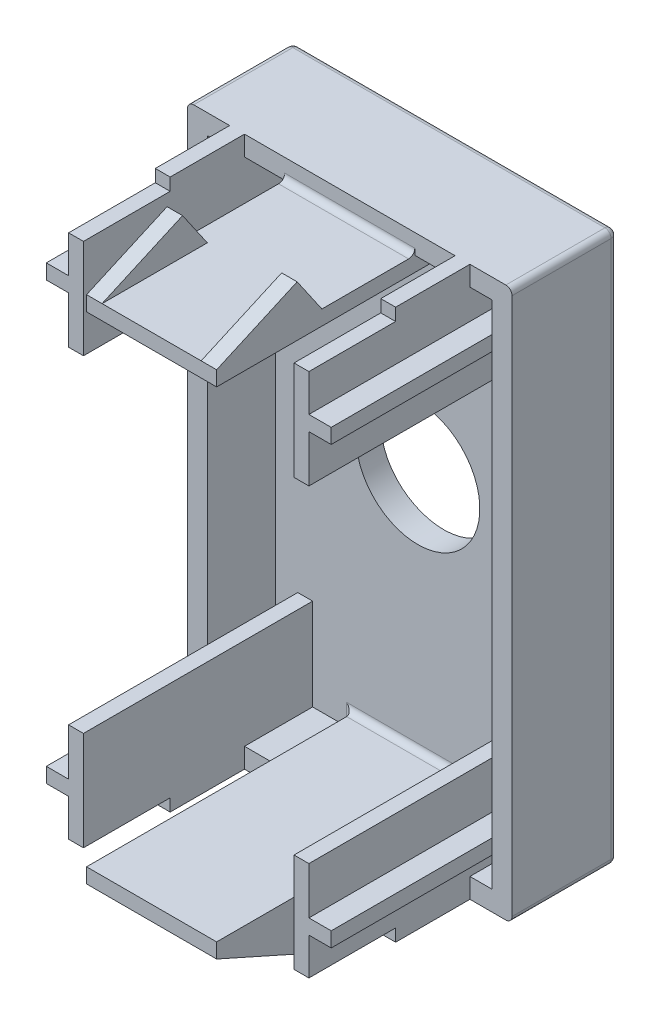
SolidWorks part; units mm, degrees
material "Сталь 3 ГОСТ 535-88"
ref_plane "Спереди" through (0, 0, 0) normal (0, 0, 1) x (1, 0, 0)
ref_plane "Сверху" through (0, 0, 0) normal (0, 1, 0) x (1, 0, 0)
ref_plane "Справа" through (0, 0, 0) normal (1, 0, 0) x (0, 0, -1)
sketch "Эскиз1" plane through (0, 0, 0) normal (0, 0, 1) x (1, 0, 0)
  line L0 (0, 22.2) -> (26.2, 22.2) construction
  line L1 (0, 0) -> (26.2, 0)
  line L2 (0, 0) -> (0, 44.4)
  line L3 (0, 44.4) -> (26.2, 44.4)
  line L4 (26.2, 0) -> (26.2, 44.4)
  circle A0 centre (13.1, 22.2) radius 5
  dimension "D3" = 10
  dimension "D1" = 26.2
  dimension "D2" = 44.4
extrude "Бобышка-Вытянуть1" add sketch "Эскиз1" along normal blind 8.5
ref_plane "Плоскость1" through (3, 0, 0) normal (1, 0, 0) x (0, 0, -1)
sketch "Эскиз2" plane through (3, 0, 0) normal (1, 0, 0) x (0, 0, -1)
  line L0 (0, 0) -> (0, 5) construction
  line L1 (0, 0) -> (0, 44.4) construction
  line L2 (0, 44.4) -> (0, 39.4) construction
  line L3 (0, 39.4) -> (0, 5)
  arc A0 (0, 5) -> (0, 39.4) centre (147.42, 22.2) cw
  dimension "D1" = 5
  dimension "D3" = 1
  dimension "D2" = 5
extrude "Вырез-Вытянуть1" cut sketch "Эскиз2" along normal offset from surface (20.2 mm away) 3 up to face at (26.2, 22.2, 4.25)
sketch "Эскиз3" plane through (0, 0, 8.5) normal (0, 0, 1) x (1, 0, 0)
  line L0 (24.6, 1.6) -> (24.6, 42.8)
  line L1 (26.2, 0) -> (0, 0) construction
  line L2 (26.2, 0) -> (26.2, 44.4) construction
  line L3 (26.2, 44.4) -> (0, 44.4) construction
  line L4 (0, 0) -> (0, 44.4) construction
  line L5 (24.6, 42.8) -> (1.6, 42.8)
  line L6 (1.6, 1.6) -> (1.6, 42.8)
  line L7 (24.6, 1.6) -> (1.6, 1.6)
  dimension "D1" = 1.6
extrude "Вырез-Вытянуть2" cut sketch "Эскиз3" against normal blind 5.5
sketch "Эскиз4" plane through (0, 0, 3) normal (0, 0, 1) x (1, 0, 0)
  line L0 (3.4, 44.4) -> (3.4, 40.4)
  line L1 (24.6, 42.8) -> (1.6, 42.8) construction
  line L2 (3.4, 40.4) -> (1.6, 40.4)
  line L3 (1.6, 42.8) -> (1.6, 1.6) construction
  line L4 (1.6, 40.4) -> (1.6, 39.2)
  line L5 (1.6, 39.2) -> (3.4, 39.2)
  line L6 (3.4, 39.2) -> (3.4, 35.4)
  line L7 (3.4, 35.4) -> (4.6, 35.4)
  line L8 (4.6, 35.4) -> (4.6, 44.4)
  line L10 (4.6, 44.4) -> (3.4, 44.4)
  line L11 (3.4, 39.2) -> (3.4, 40.4) construction
  line L12 (13.1, 42.8) -> (13.1, 1.6) construction
  line L13 (1.6, 1.6) -> (24.6, 1.6) construction
  line L14 (24.6, 22.2) -> (1.6, 22.2) construction
  line L15 (24.6, 1.6) -> (24.6, 42.8) construction
  line L16 (1.6, 42.8) -> (1.6, 1.6) construction
  line L17 (22.8, 39.2) -> (22.8, 40.4) construction
  line L18 (21.6, 44.4) -> (22.8, 44.4)
  line L19 (21.6, 35.4) -> (21.6, 44.4)
  line L20 (22.8, 35.4) -> (21.6, 35.4)
  line L21 (22.8, 39.2) -> (22.8, 35.4)
  line L22 (24.6, 39.2) -> (22.8, 39.2)
  line L23 (24.6, 40.4) -> (24.6, 39.2)
  line L24 (22.8, 40.4) -> (24.6, 40.4)
  line L25 (22.8, 44.4) -> (22.8, 40.4)
  line L26 (22.8, 5.2) -> (22.8, 4) construction
  line L27 (3.4, 5.2) -> (3.4, 4) construction
  line L28 (22.8, 0) -> (22.8, 4)
  line L29 (22.8, 4) -> (24.6, 4)
  line L30 (24.6, 4) -> (24.6, 5.2)
  line L31 (24.6, 5.2) -> (22.8, 5.2)
  line L32 (22.8, 5.2) -> (22.8, 9)
  line L33 (22.8, 9) -> (21.6, 9)
  line L34 (21.6, 9) -> (21.6, 0)
  line L35 (21.6, 0) -> (22.8, 0)
  line L36 (4.6, 0) -> (3.4, 0)
  line L37 (4.6, 9) -> (4.6, 0)
  line L38 (3.4, 9) -> (4.6, 9)
  line L39 (3.4, 5.2) -> (3.4, 9)
  line L40 (1.6, 5.2) -> (3.4, 5.2)
  line L41 (1.6, 4) -> (1.6, 5.2)
  line L42 (3.4, 4) -> (1.6, 4)
  line L43 (3.4, 0) -> (3.4, 4)
  line L44 (26.2, 44.4) -> (0, 44.4) construction
  point P48 (0, 0)
  point P49 (0, 0)
  point P50 (0, 0)
  point P51 (0, 0)
  point P52 (0, 0)
  point P53 (3.4, 44.4)
  dimension "D1" = 1.2
  dimension "D2" = 1.2
  dimension "D3" = 4
  dimension "D4" = 9
  dimension "D5" = 1.8
extrude "Бобышка-Вытянуть2" add sketch "Эскиз4" along normal blind 18.5
ref_plane "Плоскость2" through (13.1, 0, 0) normal (-1, 0, 0) x (0, 0, 1)
sketch "Эскиз6" plane through (13.1, 0, 0) normal (-1, 0, 0) x (0, 0, 1)
  line L0 (3, 1.6) -> (3, 2.8)
  line L1 (3, 9) -> (3, 1.6) construction
  line L2 (3, 2.8) -> (24.5, 2.8)
  line L3 (24.5, 2.8) -> (24.5, 1.6)
  line L4 (24.5, 1.6) -> (18, -1.3)
  line L5 (18, -1.3) -> (16, 1.6)
  line L6 (16, 1.6) -> (3, 1.6)
  line L7 (16, 1.6) -> (24.5, 1.6) construction
  line L8 (0, 22.2) -> (37.8181, 22.2) construction
  line L9 (0, 39.4) -> (0, 5) construction
  line L10 (16, 42.8) -> (24.5, 42.8) construction
  line L11 (16, 42.8) -> (3, 42.8)
  line L12 (18, 45.7) -> (16, 42.8)
  line L13 (24.5, 42.8) -> (18, 45.7)
  line L14 (24.5, 41.6) -> (24.5, 42.8)
  line L15 (3, 41.6) -> (24.5, 41.6)
  line L16 (3, 42.8) -> (3, 41.6)
  dimension "D1" = 1.2
  dimension "D2" = 13
  dimension "D3" = 21.5
  dimension "D4" = 47
  dimension "D5" = 15
extrude "Бобышка-Вытянуть3" add sketch "Эскиз6" along normal blind 5.25 and the other way blind 5.25
sketch "Эскиз7" plane through (3.4, 0, 0) normal (-1, 0, 0) x (0, 0, 1)
  line L0 (21.5, 4) -> (21.5, 0) construction
  line L1 (21.5, 44.4) -> (14.5, 44.4)
  line L2 (21.5, 44.4) -> (21.5, 43.4)
  line L3 (21.5, 43.4) -> (14.5, 43.4)
  line L4 (14.5, 44.4) -> (14.5, 43.4)
  line L5 (21.5, 0) -> (14.5, 0)
  line L6 (21.5, 0) -> (21.5, 1)
  line L7 (21.5, 1) -> (14.5, 1)
  line L8 (14.5, 0) -> (14.5, 1)
  line L9 (21.5, 0) -> (8.5, 0) construction
  dimension "D1" = 1
  dimension "D2" = 7
  dimension "D3" = 1
  dimension "D4" = 7
extrude "Вырез-Вытянуть3" cut sketch "Эскиз7" against normal blind 3
sketch "Эскиз8" plane through (22.8, 0, 0) normal (1, 0, 0) x (0, 0, -1)
  line L0 (-21.5, 44.4) -> (-8.5, 44.4) construction
  line L1 (-21.5, 0) -> (-14.5, 0)
  line L2 (-21.5, 0) -> (-21.5, 1)
  line L3 (-21.5, 1) -> (-14.5, 1)
  line L4 (-14.5, 0) -> (-14.5, 1)
  line L5 (-21.5, 44.4) -> (-14.5, 44.4)
  line L6 (-21.5, 44.4) -> (-21.5, 43.4)
  line L7 (-21.5, 43.4) -> (-14.5, 43.4)
  line L8 (-14.5, 44.4) -> (-14.5, 43.4)
  point P11 (-21.5, 42.8)
  dimension "D1" = 1
  dimension "D2" = 1
  dimension "D3" = 7
  dimension "D4" = 7
extrude "Вырез-Вытянуть4" cut sketch "Эскиз8" against normal blind 3
sketch "Эскиз9" plane through (0, 0, 24.5) normal (0, 0, 1) x (1, 0, 0)
  line L0 (13.1, 1.6) -> (13.1, 0.0848) construction
  line L1 (18.35, 1.6) -> (7.85, 1.6) construction
  line L2 (13.1, 4.675) -> (13.1, -4.675) construction
  line L3 (18.35, 2.8) -> (7.85, 2.8) construction
  line L4 (17.1, 1.6) -> (9.1, 1.6)
  line L5 (17.1, 1.6) -> (17.1, -1.4304)
  line L6 (17.1, -1.4304) -> (9.1, -1.4304)
  line L7 (9.1, 1.6) -> (9.1, -1.4304)
  line L8 (17.1, 1.6) -> (9.1, -1.4304) construction
  line L9 (17.1, -1.4304) -> (9.1, 1.6) construction
  line L10 (0, 22.2) -> (-5.4157, 22.2) construction
  line L11 (0, 44.4) -> (0, 0) construction
  line L12 (17.1, 45.8304) -> (9.1, 42.8) construction
  line L13 (17.1, 42.8) -> (9.1, 45.8304) construction
  line L14 (13.1, 42.8) -> (13.1, 44.3152) construction
  line L15 (9.1, 42.8) -> (9.1, 45.8304)
  line L16 (17.1, 45.8304) -> (9.1, 45.8304)
  line L17 (17.1, 42.8) -> (17.1, 45.8304)
  line L18 (17.1, 42.8) -> (9.1, 42.8)
  dimension "D1" = 8
  dimension "D2" = 1.2
extrude "Вырез-Вытянуть5" cut sketch "Эскиз9" against normal up to surface (16 mm away) up to face at (1.9333, 22.2, 8.5)
fillet "Скругление1" radius 0.5 8 edges at (0, 0, 4.25) (26.2, 0, 4.25) (0, 44.4, 4.25) (26.2, 44.4, 4.25) (13.1, 0, 0) (0, 22.2, 0) (13.1, 44.4, 0) (26.2, 22.2, 0)
fillet "Скругление3" radius 0.5 8 edges at (7.85, 2.2, 3) (18.35, 2.2, 3) (18.35, 42.2, 3) (7.85, 42.2, 3) (13.1, 41.6, 3) (13.1, 42.8, 8.5) (13.1, 2.8, 3) (13.1, 1.6, 8.5)
